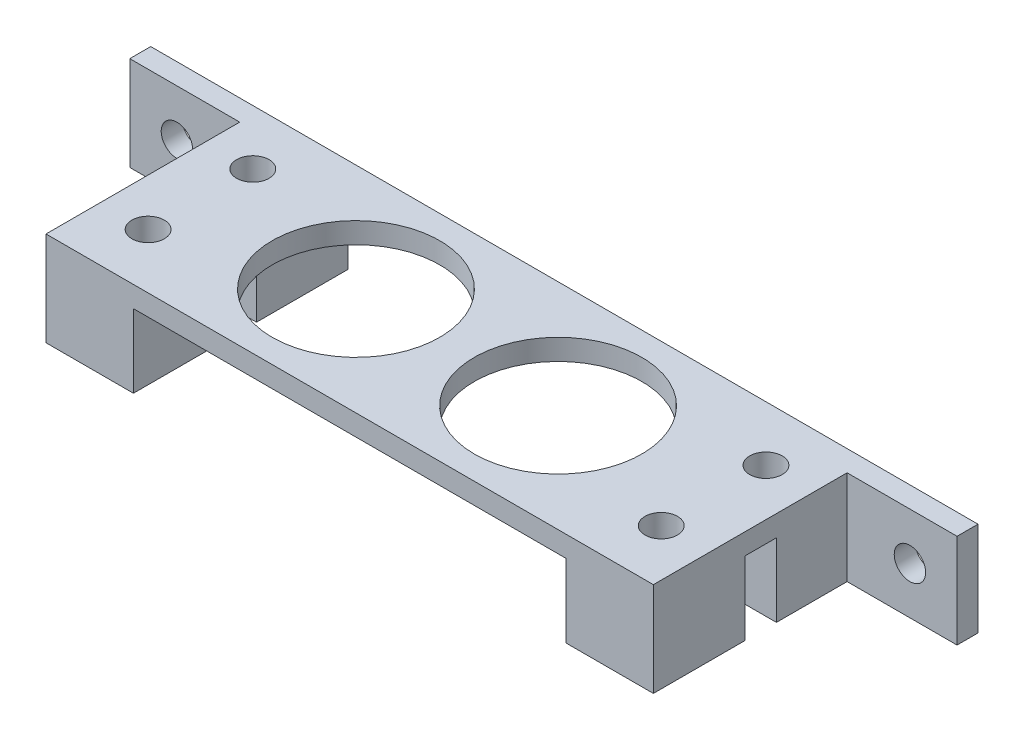
SolidWorks part; units mm, degrees
ref_plane "Front Plane" through (0, 0, 0) normal (0, 0, 1) x (1, 0, 0)
ref_plane "Top Plane" through (0, 0, 0) normal (0, 1, 0) x (1, 0, 0)
ref_plane "Right Plane" through (0, 0, 0) normal (1, 0, 0) x (0, 0, -1)
sketch "Sketch2" plane through (0, 0, 0) normal (0, 1, 0) x (1, 0, 0)
  line L0 (-24.5, 5) -> (-24.5, -5) construction
  line L1 (-29, 10.25) -> (29, 10.25)
  line L2 (-29, 10.25) -> (-29, -10.25)
  line L3 (-29, -10.25) -> (29, -10.25)
  line L4 (29, 10.25) -> (29, -10.25)
  line L5 (-29, 10.25) -> (29, -10.25) construction
  line L6 (-29, -10.25) -> (29, 10.25) construction
  line L7 (-24.5, -5) -> (24.5, -5) construction
  line L8 (24.5, -5) -> (24.5, 5) construction
  line L9 (24.5, 5) -> (-24.5, 5) construction
  line L10 (-20.65, 10.25) -> (-20.65, -10.25) construction
  line L15 (20.65, 10.25) -> (20.65, -10.25) construction
  line L16 (-20.65, 0) -> (20.65, 0) construction
  circle A0 centre (-9.65, 0) radius 8
  circle A1 centre (-24.5, 5) radius 1.55
  circle A2 centre (-24.5, -5) radius 1.55
  circle A3 centre (24.5, 5) radius 1.55
  circle A4 centre (24.5, -5) radius 1.55
  circle A5 centre (9.65, 0) radius 8
  point P0 (0, 0)
  point P16 (-24.5, 0)
  point P17 (0, 5)
  point P27 (0, 0)
  dimension "D1" = 16
  dimension "D2" = 3.1
  dimension "D9" = 41.3
  dimension "D10" = 11
  dimension "D3" = 4.5
  dimension "D4" = 10
  dimension "D5" = 49
  dimension "D6" = 20.5
  dimension "D7" = 11
extrude "Boss-Extrude1" add sketch "Sketch2" along normal blind 2 contours L4 L1 L2 L3 A4 A3 A2 A1 A0 region at (0, 0, 0)
sketch "Sketch3" plane through (0, 0, 0) normal (0, -1, 0) x (1, 0, 0)
  line L0 (-20.65, 10.25) -> (-20.65, -10.25)
  line L1 (-29, 10.25) -> (29, 10.25) construction
  line L2 (-29, -10.25) -> (29, -10.25) construction
  line L3 (-20.65, -10.25) -> (-29, -10.25)
  line L4 (-29, -10.25) -> (-29, 10.25)
  line L5 (-29, 10.25) -> (-20.65, 10.25)
  line L6 (20.65, 10.25) -> (20.65, -10.25)
  line L7 (20.65, -10.25) -> (29, -10.25)
  line L8 (29, -10.25) -> (29, 10.25)
  line L9 (29, 10.25) -> (20.65, 10.25)
  line L10 (-29, 10.25) -> (29, 10.25) construction
  line L12 (-29, 1.5) -> (-20.65, 1.5)
  line L13 (-29, 1.5) -> (-29, -1.5)
  line L14 (-29, -1.5) -> (-20.65, -1.5)
  line L15 (-20.65, 1.5) -> (-20.65, -1.5)
  line L16 (20.65, 1.5) -> (29, 1.5)
  line L17 (20.65, 1.5) -> (20.65, -1.5)
  line L18 (20.65, -1.5) -> (29, -1.5)
  line L19 (29, 1.5) -> (29, -1.5)
  circle A0 centre (-24.5, -5) radius 1.55
  circle A1 centre (-24.5, 5) radius 1.55
  circle A2 centre (24.5, -5) radius 1.55
  circle A3 centre (24.5, 5) radius 1.55
  point P43 (20.65, 0)
  point P44 (-20.65, 0)
  circle M5 centre (24.5, 5) radius 1.55
  circle M6 centre (24.5, -5) radius 1.55
  circle M7 centre (-24.5, 5) radius 1.55
  circle M8 centre (-24.5, -5) radius 1.55
  line M13 (29, -10.25) -> (29, 10.25)
  line M14 (29, 10.25) -> (-29, 10.25)
  line M15 (-29, 10.25) -> (-29, -10.25)
  line M16 (-29, -10.25) -> (29, -10.25)
  dimension "D1" = 3
extrude "Boss-Extrude2" add sketch "Sketch3" along normal blind 7 contours L12 L0 M15 M14 M7 | L14 L0 M15 M16 M8 | L6 L16 L8 M14 M5 | L18 L6 M16 M13 M6 region at (-20.7709, 0, 5.875) region at (24.825, 0, 10.1291) region at (-20.7709, 0, -5.875) region at (24.825, 0, -1.6209)
sketch "Sketch4" plane through (0, 0, -10.25) normal (0, 0, -1) x (-1, 0, 0)
  line L0 (35, -2.5) -> (-35, -2.5) construction
  line L1 (39.5, 2) -> (-39.5, 2)
  line L2 (39.5, 2) -> (39.5, -7)
  line L3 (39.5, -7) -> (-39.5, -7)
  line L4 (-39.5, 2) -> (-39.5, -7)
  line L5 (29, 2) -> (29, -7) construction
  line L6 (-20.65, -7) -> (-29, -7) construction
  line L7 (20.65, -7) -> (20.65, 0)
  line L8 (20.65, 0) -> (-20.65, 0)
  line L9 (-20.65, -7) -> (-20.65, 0) construction
  line L10 (20.65, 0) -> (-20.65, 0) construction
  line L11 (-20.65, 0) -> (-20.65, -7)
  line L12 (29, 2) -> (29, -7)
  line L13 (-29, 2) -> (-29, -7)
  circle A0 centre (35, -2.5) radius 1.5
  circle A1 centre (-35, -2.5) radius 1.5
  point P6 (0, 2)
  point P7 (0, -2.5)
  point P16 (29, -2.5)
  dimension "D1" = 3
  dimension "D2" = 6
  dimension "D3" = 4.5
extrude "Boss-Extrude3" add sketch "Sketch4" against normal blind 2 contours L1 L4 L3 A1 L6 | A0 L11 L3 L2 L1 region at (-39.3617, -2.5, -10.25) region at (29.1383, -2.5, -10.25)
